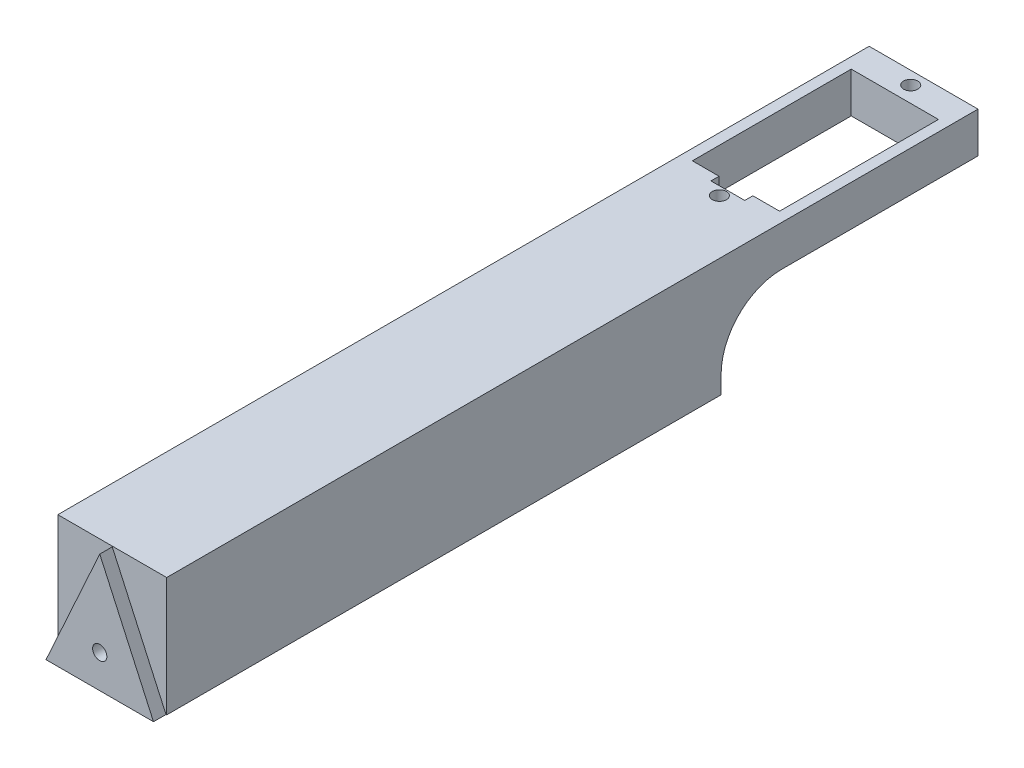
SolidWorks part; units mm, degrees
ref_plane "Ebene vorne" through (0, 0, 0) normal (0, 0, 1) x (1, 0, 0)
ref_plane "Ebene oben" through (0, 0, 0) normal (0, 1, 0) x (1, 0, 0)
ref_plane "Ebene rechts" through (0, 0, 0) normal (1, 0, 0) x (0, 0, -1)
sketch "Skizze1" plane through (0, 0, 0) normal (0, 1, 0) x (1, 0, 0)
  line L1 (-8.05, -60) -> (8.05, -60)
  line L2 (-8.05, -60) -> (-8.05, 60)
  line L3 (-8.05, 60) -> (8.05, 60)
  line L4 (8.05, -60) -> (8.05, 60)
  line L5 (-8.05, -60) -> (8.05, 60) construction
  line L6 (-8.05, 60) -> (8.05, -60) construction
  point P0 (0, 0)
  dimension "D1" = 120
  dimension "D2" = 16.1
extrude "Aufsatz-Linear austragen1" add sketch "Skizze1" along normal blind 17.6
sketch "Skizze2" plane through (0, 0, 60) normal (0, 0, 1) x (1, 0, 0)
  line L0 (0, 17.5) -> (-7.95, 0)
  line L1 (0, -9.68) -> (0, 9.68) construction
  line L2 (-8.05, 0) -> (8.05, 0) construction
  line L3 (-7.95, 0) -> (7.95, 0)
  line L4 (7.95, 0) -> (0, 17.5)
  line L5 (-8.05, 17.6) -> (8.05, 17.6) construction
  line L7 (8.05, 17.6) -> (8.05, 0) construction
  line L8 (-8.05, 17.6) -> (-8.05, 0) construction
  dimension "D1" = 0.1
  dimension "D2" = 0.1
  dimension "D3" = 0.1
extrude "Aufsatz-Linear austragen2" add sketch "Skizze2" along normal blind 1.85
sketch "Skizze3" plane through (0, 0, 61.85) normal (0, 0, 1) x (1, 0, 0)
  line L0 (0, -9.68) -> (0, 9.68) construction
  line L1 (0, 3.84) -> (3.3257, 3.84) construction
  line L2 (-7.95, 0) -> (7.95, 0) construction
  circle A0 centre (0, 4.89) radius 1.05
  dimension "D1" = 2.1
  dimension "D2" = 3.84
extrude "Schnitt-Linear austragen1" cut sketch "Skizze3" against normal blind 13
sketch "Skizze4" plane through (0, 17.6, 0) normal (0, 1, 0) x (1, 0, 0)
  line L0 (0, -9.68) -> (0, 9.68) construction
  line L1 (-6.45, 32.25) -> (-2.5, 32.25)
  line L2 (-6.45, 32.25) -> (-6.45, 55.75)
  line L3 (-6.45, 55.75) -> (6.45, 55.75)
  line L4 (6.45, 32.25) -> (6.45, 55.75)
  line L5 (-6.45, 32.25) -> (6.45, 55.75) construction
  line L6 (-6.45, 55.75) -> (6.45, 32.25) construction
  line L7 (2.5, 32.25) -> (6.45, 32.25)
  line L8 (8.05, 60) -> (-8.05, 60) construction
  line L9 (0, 30.85) -> (5.5865, 30.85) construction
  line L10 (0, 57.05) -> (4.8773, 57.05) construction
  line L12 (-2.5, 32.25) -> (-2.5, 31.05)
  line L13 (-2.5, 31.05) -> (2.5, 31.05)
  line L14 (2.5, 32.25) -> (2.5, 31.05)
  circle A0 centre (0, 58.1) radius 1.05
  circle A1 centre (0, 29.8) radius 1.05
  point P0 (0, 44)
  point P21 (0, 0)
  dimension "D1" = 2.1
  dimension "D2" = 2.1
  dimension "D3" = 23.5
  dimension "D4" = 12.9
  dimension "D5" = 16
  dimension "D6" = 1.4
  dimension "D7" = 1.3
  dimension "D8" = 1.2
  dimension "D9" = 5
  dimension "D10" = 2.5
extrude "Schnitt-Linear austragen2" cut sketch "Skizze4" against normal through all
sketch "Skizze5" plane through (8.05, 0, 0) normal (1, 0, 0) x (0, 0, -1)
  line L0 (60, 11.6) -> (31, 11.6)
  line L1 (60, 17.6) -> (60, 0) construction
  line L2 (22, 2.6) -> (22, 0)
  line L3 (8.855, 0) -> (-8.855, 0) construction
  line L4 (22, 0) -> (60, 0)
  line L5 (60, 0) -> (60, 11.6)
  line L6 (-60, 17.6) -> (60, 17.6) construction
  arc A0 (31, 11.6) -> (22, 2.6) centre (31, 2.6) ccw
  dimension "D3" = 9
  dimension "D1" = 38
  dimension "D2" = 6
extrude "Schnitt-Linear austragen3" cut sketch "Skizze5" against normal through all
